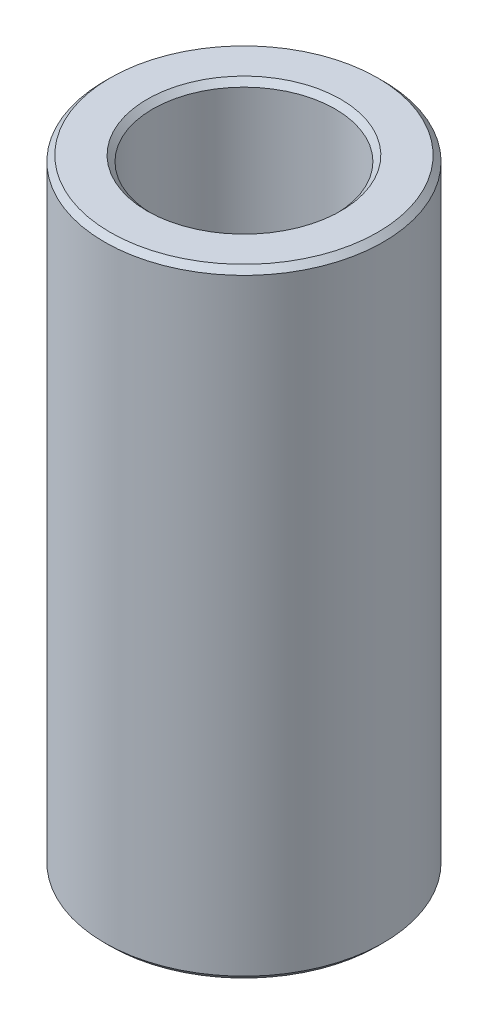
SolidWorks part; units mm, degrees
ref_plane "Front Plane" through (0, 0, 0) normal (0, 0, 1) x (1, 0, 0)
ref_plane "Top Plane" through (0, 0, 0) normal (0, 1, 0) x (1, 0, 0)
ref_plane "Right Plane" through (0, 0, 0) normal (1, 0, 0) x (0, 0, -1)
sketch "Sketch1" plane through (0, 0, 0) normal (0, 1, 0) x (1, 0, 0)
  circle A0 centre (0, 0) radius 47.5
  dimension "SLEEVE_OD" = 95
extrude "Boss-Extrude1" add sketch "Sketch1" along normal blind 210.6446
sketch "Sketch2" plane through (0, 0, 0) normal (0, 1, 0) x (1, 0, 0)
  circle A0 centre (0, 0) radius 31.0821
  dimension "BORE_D" = 62.1641
extrude "Cut-Extrude1" cut sketch "Sketch2" along normal through all
chamfer "Chamfer1" distance 1.9136 angle 45 4 edges at (0, 210.6446, 31.0821) (0, 0, 31.0821) (0, 0, 47.5) (0, 210.6446, 47.5)
